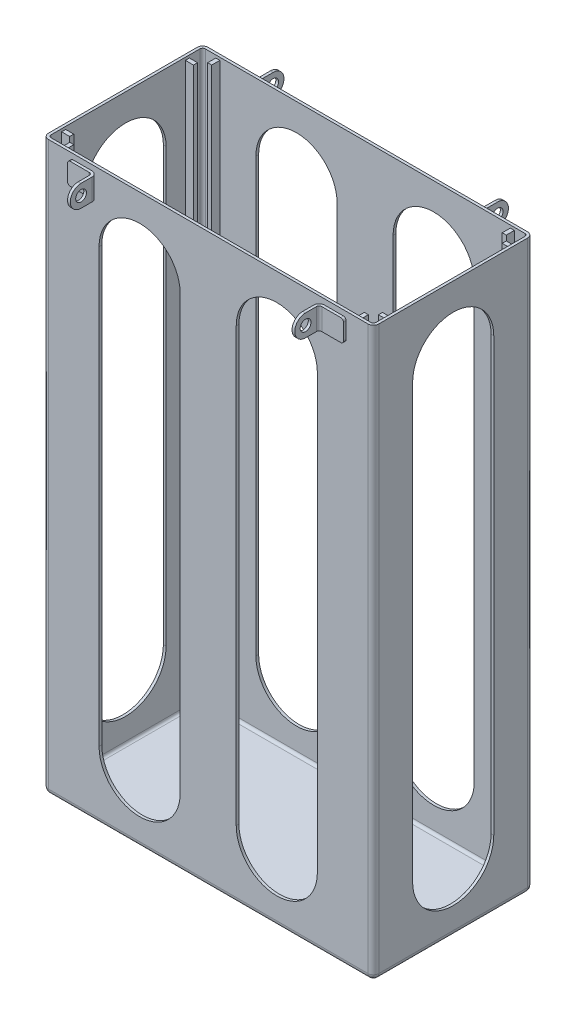
SolidWorks part; units mm, degrees
ref_plane "Front Plane" through (0, 0, 0) normal (0, 0, 1) x (1, 0, 0)
ref_plane "Top Plane" through (0, 0, 0) normal (0, 1, 0) x (1, 0, 0)
ref_plane "Right Plane" through (0, 0, 0) normal (1, 0, 0) x (0, 0, -1)
sketch "Sketch2" plane through (0, 0, 0) normal (0, 1, 0) x (1, 0, 0)
  line L0 (-104.65, 50) -> (-104.65, 41.5) construction
  line L1 (-113.15, -50) -> (113.15, -50) construction
  line L2 (-113.15, -50) -> (-113.15, 50) construction
  line L3 (-113.15, 50) -> (113.15, 50) construction
  line L4 (113.15, -50) -> (113.15, 50) construction
  line L5 (-113.15, -50) -> (113.15, 50) construction
  line L6 (-113.15, 50) -> (113.15, -50) construction
  line L7 (-110.4, 51) -> (-107.4, 51)
  line L8 (-110.4, 51) -> (-110.4, 57)
  line L9 (-110.4, 57) -> (-107.4, 57)
  line L10 (-107.4, 51) -> (-107.4, 57)
  line L11 (-114.15, 47.25) -> (-120.15, 47.25)
  line L12 (-114.15, 47.25) -> (-114.15, 44.25)
  line L13 (-114.15, 44.25) -> (-120.15, 44.25)
  line L14 (-120.15, 47.25) -> (-120.15, 44.25)
  line L15 (-104.65, 41.5) -> (-113.15, 41.5) construction
  line L16 (-108.9, 41.5) -> (-108.9, 51) construction
  line L17 (-104.65, 45.75) -> (-114.15, 45.75) construction
  line L18 (-110.4, 51) -> (-110.4, 50) construction
  line L19 (-110.4, 50) -> (-113.15, 47.25) construction
  line L20 (-113.15, 47.25) -> (-114.15, 47.25) construction
  point P0 (0, 0)
  dimension "D1" = 226.3
  dimension "D2" = 100
  dimension "D3" = 8.5
  dimension "D4" = 1
  dimension "D5" = 3
  dimension "D6" = 6
extrude "Boss-Extrude1" add sketch "Sketch2" along normal mid plane 416
mirror "Mirror2" about plane through (0, 0, 0) normal (0, 0, 1) of bodies 113 114
mirror "Mirror3" about plane through (0, 0, 0) normal (1, 0, 0) of bodies 114 115 113 116
sketch "Sketch3" plane through (0, 0, 0) normal (0, 1, 0) x (1, 0, 0)
  line L0 (120.15, -47.25) -> (120.15, -44.25) construction
  line L1 (-120.15, 57) -> (120.15, 57)
  line L2 (-120.15, 57) -> (-120.15, -57)
  line L3 (-120.15, -57) -> (120.15, -57)
  line L4 (120.15, 57) -> (120.15, -57)
  line L5 (107.4, -57) -> (110.4, -57) construction
  line L6 (-107.4, 57) -> (-110.4, 57) construction
  line L7 (-120.15, 47.25) -> (-120.15, 44.25) construction
  point P10 (0, 0)
extrude "Extrude-Thin1" add sketch "Sketch3" along normal mid plane 420 separate body thin thin type one direction wall 2
sketch "Sketch4" plane through (0, -208, 0) normal (0, -1, 0) x (1, 0, 0)
  line L16 (-122.15, 59) -> (-122.15, -59)
  line L17 (-122.15, -59) -> (122.15, -59)
  line L18 (122.15, -59) -> (122.15, 59)
  line L19 (122.15, 59) -> (-122.15, 59)
  line L20 (-122.15, 59) -> (-122.15, -59)
  line L21 (-122.15, -59) -> (122.15, -59)
  line L22 (122.15, -59) -> (122.15, 59)
  line L23 (122.15, 59) -> (-122.15, 59)
  dimension "D1" = 0
extrude "Boss-Extrude2" add sketch "Sketch4" along normal blind 2
sketch "Sketch5" plane through (0, 0, 59) normal (0, 0, 1) x (1, 0, 0)
  line L0 (-50.7167, -160) -> (-50.7167, 160) construction
  line L1 (-80.7167, -160) -> (-80.7167, 160)
  line L2 (-20.7167, -160) -> (-20.7167, 160)
  line L3 (50.7167, -160) -> (50.7167, 160) construction
  line L4 (20.7167, -160) -> (20.7167, 160)
  line L5 (80.7167, -160) -> (80.7167, 160)
  line L6 (-50.7167, 0) -> (50.7167, 0) construction
  line L7 (20.7167, 0) -> (-20.7167, 0) construction
  line L8 (-80.7167, 0) -> (-122.15, 0) construction
  line L9 (-122.15, 210) -> (-122.15, -210) construction
  arc A0 (-80.7167, -160) -> (-20.7167, -160) centre (-50.7167, -160) ccw
  arc A1 (-20.7167, 160) -> (-80.7167, 160) centre (-50.7167, 160) ccw
  arc A2 (20.7167, -160) -> (80.7167, -160) centre (50.7167, -160) ccw
  arc A3 (80.7167, 160) -> (20.7167, 160) centre (50.7167, 160) ccw
  point P2 (-50.7167, 0)
  point P8 (50.7167, 0)
  dimension "D1" = 60
  dimension "D2" = 320
extrude "Cut-Extrude1" cut sketch "Sketch5" against normal through all
sketch "Sketch6" plane through (122.15, 0, 0) normal (1, 0, 0) x (0, 0, -1)
  line L0 (0, -160) -> (0, 160) construction
  line L1 (-30, -160) -> (-30, 160)
  line L2 (30, -160) -> (30, 160)
  arc A0 (-30, -160) -> (30, -160) centre (0, -160) ccw
  arc A1 (30, 160) -> (-30, 160) centre (0, 160) ccw
  point P2 (0, 0)
  dimension "D2" = 60
extrude "Cut-Extrude2" cut sketch "Sketch6" against normal through all
sketch "Sketch7" plane through (0, 210, 0) normal (0, 1, 0) x (1, 0, 0)
  line L0 (-102, 59) -> (-82, 59)
  line L1 (122.15, 59) -> (-122.15, 59) construction
  line L2 (-82, 59) -> (-82, 79)
  dimension "D1" = 82
  dimension "D2" = 20
extrude "Extrude-Thin2" add sketch "Sketch7" against normal blind 16 from offset 4 separate body thin offset against normal yes thin type one direction reverse wall 2
fillet "Fillet1" 2 edges at (-83, 206, -79) (-83, 190, -79) type full round first side face at (-89.3333, 206, -66.3333) second side face at (-89.3333, 190, -66.3333) middle face at (-83, 198, -79)
hole_wizard "Ø8.0mm Dowel Hole1" positions "Sketch8" profile "Sketch9" hole size "Ø8.0" standard "ISO" end condition through all
sketch "Sketch8" plane through (-82, 0, 0) normal (1, 0, 0) x (0, 0, -1)
  point P0 (71, 198)
sketch "Sketch9" plane through (-82, 198, -71) normal (0, 1, 0) x (0, 0, -1)
  line L0 (0, 0) -> (0, 40.15)
  line L1 (0, 40.15) -> (4, 40.15)
  line L2 (4, 40.15) -> (4, 0)
  line L5 (4, 0) -> (0, 0)
  line L11 (0, -6.35) -> (0, 107.95) construction
  dimension "Thru Hole Dia." = 8
  dimension "Thru Hole Depth" = 40.15
fillet "Fillet2" radius 2 3 edges at (-84, 198, -61) (-102, 190, -60) (-102, 206, -60)
fillet "Fillet3" radius 4 1 edges at (-82, 198, -59)
mirror "Mirror4" about plane through (0, 0, 0) normal (1, 0, 0) of bodies 126
mirror "Mirror5" about plane through (0, 0, 0) normal (0, 0, 1) of bodies 127 126
fillet "Fillet4" radius 2 8 edges at (0, -208, -57) (120.15, -208, 0) (0, -208, 57) (-120.15, -208, 0) (120.15, 1, 57) (120.15, 1, -57) (-120.15, 1, -57) (-120.15, 1, 57)
fillet "Fillet5" radius 4 8 edges at (0, -210, 59) (122.15, -210, 0) (0, -210, -59) (-122.15, -210, 0) (-122.15, 0, -59) (122.15, 0, 59) (-122.15, 0, 59) (122.15, 0, -59)
